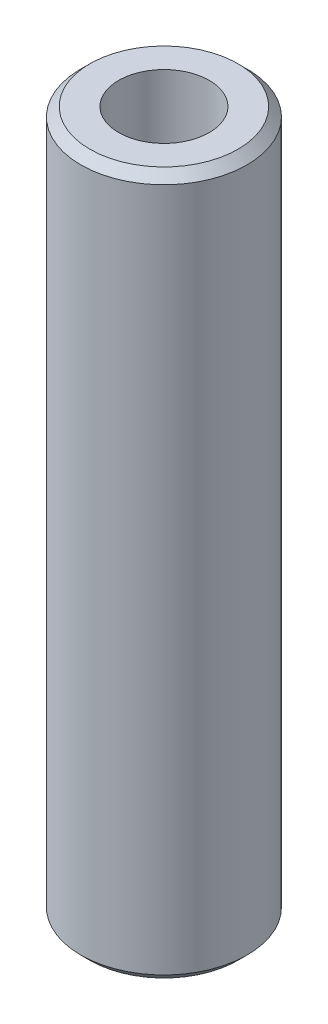
SolidWorks part; units mm, degrees
ref_plane "Front Plane" through (0, 0, 0) normal (0, 0, 1) x (1, 0, 0)
ref_plane "Top Plane" through (0, 0, 0) normal (0, 1, 0) x (1, 0, 0)
ref_plane "Right Plane" through (0, 0, 0) normal (1, 0, 0) x (0, 0, -1)
sketch "Sketch1" plane through (0, 0, 0) normal (0, 1, 0) x (1, 0, 0)
  circle A0 centre (0, 0) radius 55
  dimension "SHAFT_OD" = 110
extrude "Boss-Extrude1" add sketch "Sketch1" along normal blind 464.7778
sketch "Sketch2" plane through (0, 0, 0) normal (0, 1, 0) x (1, 0, 0)
  circle A0 centre (0, 0) radius 29.9629
  dimension "BORE_D" = 59.9258
extrude "Cut-Extrude1" cut sketch "Sketch2" along normal through all
chamfer "Chamfer1" distance 5.9823 angle 45 2 edges at (0, 464.7778, 55) (0, 0, 55)
